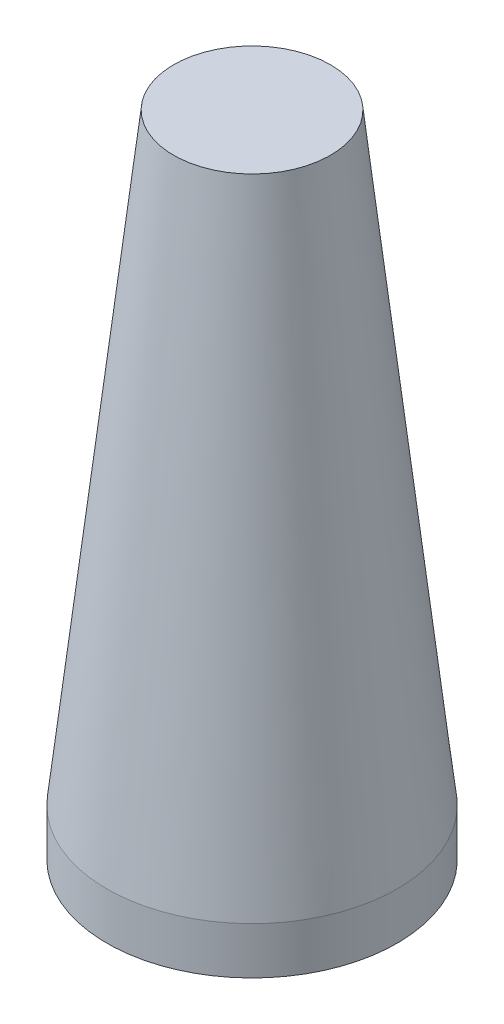
SolidWorks part; units mm, degrees
ref_plane "Front Plane" through (0, 0, 0) normal (0, 0, 1) x (1, 0, 0)
ref_plane "Top Plane" through (0, 0, 0) normal (0, 1, 0) x (1, 0, 0)
ref_plane "Right Plane" through (0, 0, 0) normal (1, 0, 0) x (0, 0, -1)
sketch "Sketch1" plane through (0, 0, 0) normal (0, 0, 1) x (1, 0, 0)
  line L0 (0, -27.499) -> (0, 800) construction
  line L1 (-178, 32.501) -> (-178, -27.499)
  line L3 (0, 800) -> (-100, 800)
  line L4 (-185, -27.499) -> (-185, 32.501)
  line L5 (0, 790) -> (-94.0647, 790)
  line L7 (-178, -27.499) -> (-185, -27.499)
  line L8 (-100, 800) -> (-185, 32.501)
  line L9 (-94.0647, 790) -> (-178, 32.501)
  point P4 (0, 0)
  point P5 (-178, -203.8262)
  point P9 (0, 0)
  point P10 (0, 0)
  dimension "D5" = 60
  dimension "D6" = 10
  dimension "D1" = 27.499
  dimension "D2" = 800
  dimension "D3" = 100
  dimension "D4" = 185
  dimension "D8" = 7
  dimension "D7" = 60
  dimension "D9" = 7
revolve "Revolve1" add sketch "Sketch1" angle 360 about L0 region at (-47.0323, 798.4793, 0)
